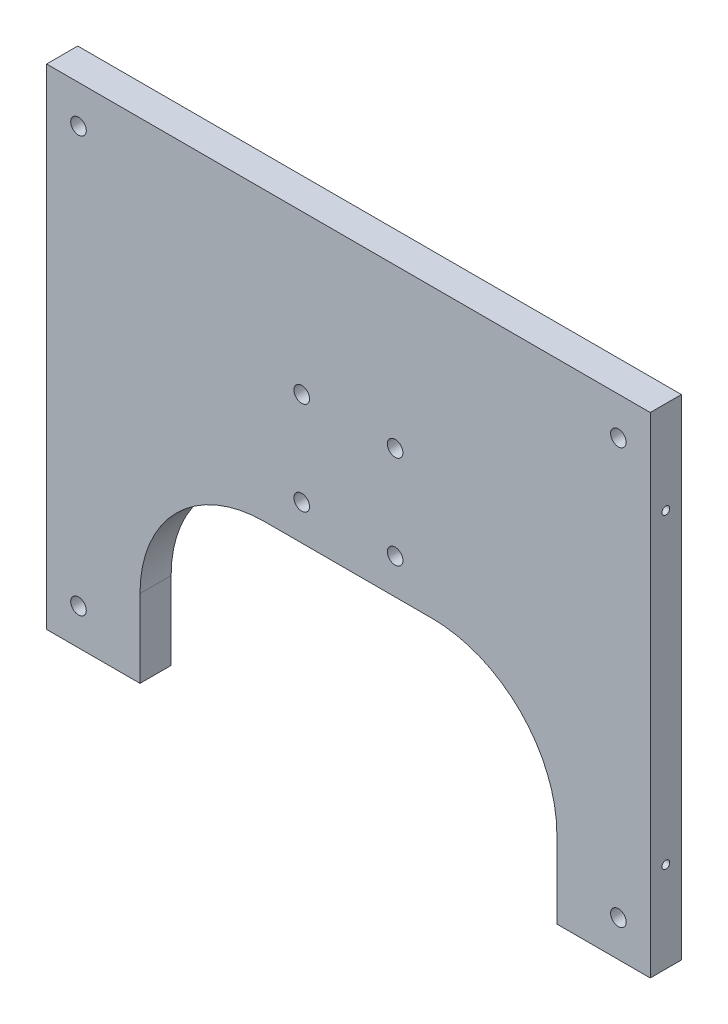
SolidWorks part; units mm, degrees
material "Beech"
ref_plane "Front Plane" through (0, 0, 0) normal (0, 0, 1) x (1, 0, 0)
ref_plane "Top Plane" through (0, 0, 0) normal (0, 1, 0) x (1, 0, 0)
ref_plane "Right Plane" through (0, 0, 0) normal (1, 0, 0) x (0, 0, -1)
sketch "Sketch1" plane through (0, 0, 0) normal (0, 0, 1) x (1, 0, 0)
  line L0 (258.9335, 10.7139) -> (12.7, 10.7139)
  line L1 (135.8167, -73.0143) -> (135.8167, 40.1583) construction
  line L2 (12.7, 10.7139) -> (12.7, -189.0518)
  line L3 (12.7, -189.0518) -> (50.8, -189.0518)
  line L4 (50.8, -189.0518) -> (50.8, -106.5018)
  line L5 (50.8, -106.5018) -> (220.8335, -106.5018)
  line L6 (135.8167, -205.9834) -> (135.8167, -73.0143) construction
  line L7 (135.8167, -106.5018) -> (135.8167, 10.7139) construction
  line L8 (271.3655, 10.7139) -> (0, 10.7139) construction
  line L9 (12.7, -189.0518) -> (12.7, 10.2705) construction
  line L10 (220.8335, -189.0518) -> (220.8335, -106.5018)
  line L11 (258.9335, -189.0518) -> (220.8335, -189.0518)
  line L12 (258.9335, 10.7139) -> (258.9335, -189.0518)
  dimension "D1" = 38.1
  dimension "D2" = 82.55
extrude "Boss-Extrude1" add sketch "Sketch1" against normal blind 12.7
hole_wizard "1/4 (0.25) Diameter Hole1" positions "Sketch4" profile "Sketch5" hole size "1/4" standard "ANSI Inch" end condition through all
sketch "Sketch4" plane through (0, 0, -12.7) normal (0, 0, -1) x (-1, 0, 0)
  point P0 (-25.7062, -174.2334)
  point P6 (-116.7667, -92.0643)
  point P9 (-154.8667, -92.0643)
  point P12 (-245.9273, -174.2334)
  point P15 (-154.8667, -53.9643)
  point P18 (-245.9273, -4.748)
  point P21 (-116.7667, -53.9643)
  point P24 (-25.7062, -4.748)
sketch "Sketch5" plane through (25.7062, -174.2334, -12.7) normal (1, 0, 0) x (0, 1, 0)
  line L0 (0, 0) -> (0, 12.7)
  line L1 (0, 12.7) -> (3.175, 12.7)
  line L2 (3.175, 12.7) -> (3.175, 0)
  line L5 (3.175, 0) -> (0, 0)
  line L11 (0, -6.35) -> (0, 107.95) construction
  dimension "Thru Hole Dia." = 6.35
  dimension "Thru Hole Depth" = 12.7
fillet "Fillet2" radius 50.8 2 edges at (220.8335, -106.5018, -6.35) (50.8, -106.5018, -6.35)
hole_wizard "Hole1" positions "Sketch6" profile "Sketch7" legacy
sketch "Sketch6" plane through (0, 1062.0089, 394.3969) normal (-1, 0, 0) x (0, -0.2641, -0.9645)
  point P29 (707.1666, 1065.2704)
  point P31 (674.128, 944.6031)
  point P35 (0, 0)
  point P36 (0, 0)
  point P37 (0, 0)
sketch "Sketch7" plane through (0, -152.1935, -6.35) normal (0, 1, 0) x (0, 0, 1)
  line L0 (0, 0) -> (0, 39.0539)
  line L1 (0, 39.0539) -> (1.5875, 38.1)
  line L2 (1.5875, 38.1) -> (1.5875, 4.0177)
  line L3 (1.5875, 4.0177) -> (5.08, 0)
  line L4 (5.08, 0) -> (0, 0)
  line L5 (0, -14.3089) -> (0, 102.4216) construction
  line L6 (0, 39.0539) -> (-1.5875, 38.1) construction
  line L7 (-1.5875, 4.0177) -> (-5.08, 0) construction
  dimension "Diameter" = 3.175
  dimension "Depth" = 38.1
  dimension "C-Sink Diameter" = 10.16
  dimension "C-Sink Angle" = 82
  dimension "Drill Angle" = 118
ref_plane "Plane1" through (135.8167, 0, 0) normal (-1, 0, 0) x (0, 0, 1)
mirror "Mirror1" about plane through (135.8167, 0, 0) normal (-1, 0, 0) of "Hole1"
